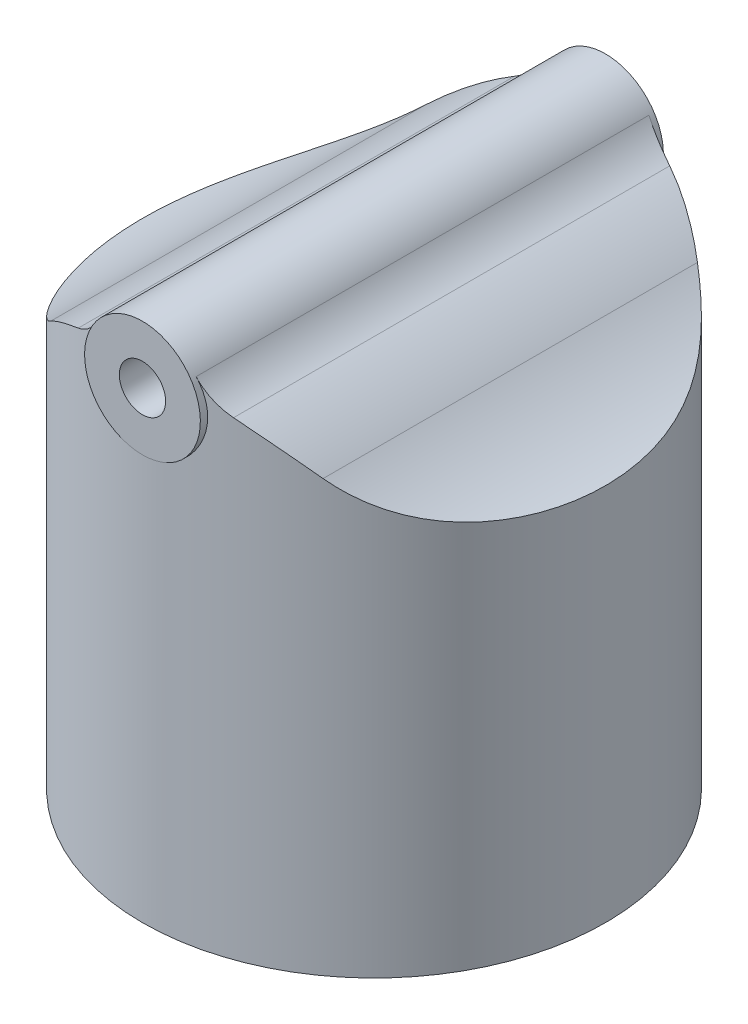
SolidWorks part; units mm, degrees
ref_plane "Front Plane" through (0, 0, 0) normal (0, 0, 1) x (1, 0, 0)
ref_plane "Top Plane" through (0, 0, 0) normal (0, 1, 0) x (1, 0, 0)
ref_plane "Right Plane" through (0, 0, 0) normal (1, 0, 0) x (0, 0, -1)
sketch "Sketch1" plane through (0, 0, 0) normal (0, 1, 0) x (1, 0, 0)
  circle A0 centre (0, 0) radius 500
  dimension "D1" = 1000
extrude "Boss-Extrude1" add sketch "Sketch1" along normal blind 1000
ref_point "Point1"
sketch "Sketch2" plane through (0, 0, 0) normal (0, 0, 1) x (1, 0, 0)
  circle A0 centre (0, 1000) radius 125
  dimension "D1" = 250
extrude "Boss-Extrude2" add sketch "Sketch2" along normal through all and the other way through all
sketch "Sketch3" plane through (0, 0, 500) normal (0, 0, 1) x (1, 0, 0)
  circle A0 centre (0, 1000) radius 50
  dimension "D1" = 100
extrude "Cut-Extrude1" cut sketch "Sketch3" against normal through all both and the other way through all
fillet "Fillet1" radius 150 2 edges at (125, 1000, 0) (-125, 1000, 0)
ref_point "Point2"
sketch "Sketch4" plane through (0, 1000, 0) normal (0, 1, 0) x (1, 0, 0)
  line L1 (-230.4886, -443.706) -> (-230.4886, 443.706)
  line L2 (-230.4886, -443.706) -> (-230.4886, 443.706)
  line L3 (230.4886, 443.706) -> (230.4886, -443.706)
  line L4 (230.4886, 443.706) -> (230.4886, -443.706)
  arc A1 (-230.4886, 443.706) -> (-230.4886, -443.706) centre (0, 0) ccw
  arc A2 (-230.4886, 443.706) -> (-230.4886, -443.706) centre (0, 0) ccw
  arc A3 (230.4886, -443.706) -> (230.4886, 443.706) centre (0, 0) ccw
  arc A4 (230.4886, -443.706) -> (230.4886, 443.706) centre (0, 0) ccw
  dimension "D1" = 0
  dimension "D2" = 0
extrude "Cut-Extrude2" cut sketch "Sketch4" against normal blind 200
fillet "Fillet2" radius 500 2 edges at (230.4886, 800, 0) (-230.4886, 800, 0)
fillet "Fillet3" radius 500 2 edges at (230.4886, 1000, 0) (-230.4886, 1000, 0)
